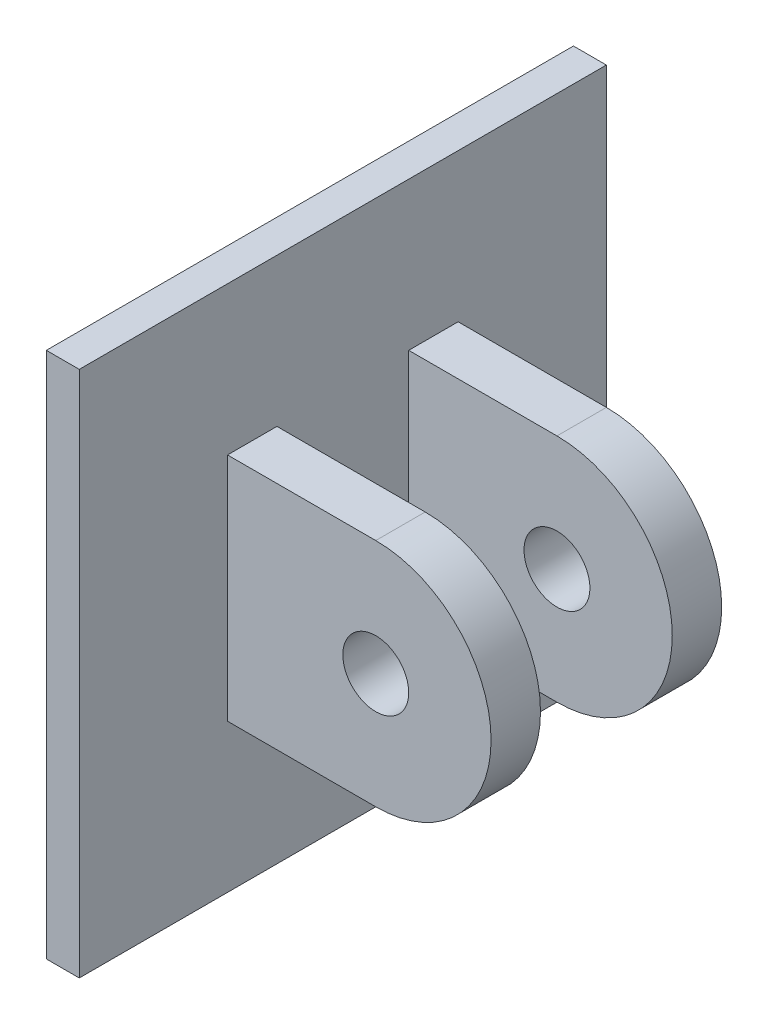
SolidWorks part; units mm, degrees
ref_plane "Front Plane" through (0, 0, 0) normal (0, 0, 1) x (1, 0, 0)
ref_plane "Top Plane" through (0, 0, 0) normal (0, 1, 0) x (1, 0, 0)
ref_plane "Right Plane" through (0, 0, 0) normal (1, 0, 0) x (0, 0, -1)
sketch "Sketch1" plane through (0, 0, 0) normal (1, 0, 0) x (0, -1, 0)
  line L1 (-50.8, -50.8) -> (50.8, -50.8)
  line L2 (-50.8, -50.8) -> (-50.8, 50.8)
  line L3 (-50.8, 50.8) -> (50.8, 50.8)
  line L4 (50.8, -50.8) -> (50.8, 50.8)
  line L5 (-50.8, -50.8) -> (50.8, 50.8) construction
  line L6 (-50.8, 50.8) -> (50.8, -50.8) construction
  dimension "D1" = 101.6
  dimension "D2" = 101.6
extrude "Boss-Extrude1" add sketch "Sketch1" along normal blind 6.35 contours L3 L4 L1 L2
sketch "Sketch2" plane through (6.35, 0, 0) normal (1, 0, 0) x (0, -1, 0)
  line L0 (0, 0) -> (0, 50.8) construction
  line L1 (-50.8, 50.8) -> (50.8, 50.8) construction
  line L2 (0, 0) -> (-50.8, 0) construction
  line L3 (-50.8, -50.8) -> (-50.8, 50.8) construction
  line L4 (-22.225, 12.7) -> (22.225, 22.225) construction
  line L5 (-22.225, 22.225) -> (22.225, 12.7) construction
  line L6 (22.225, 22.225) -> (22.225, 12.7)
  line L7 (-22.225, 12.7) -> (22.225, 12.7)
  line L8 (-22.225, 22.225) -> (-22.225, 12.7)
  line L9 (-22.225, 22.225) -> (22.225, 22.225)
  line L15 (-22.225, -22.225) -> (22.225, -22.225)
  line L16 (-22.225, -22.225) -> (-22.225, -12.7)
  line L17 (-22.225, -12.7) -> (22.225, -12.7)
  line L18 (22.225, -22.225) -> (22.225, -12.7)
  line L19 (-22.225, -22.225) -> (22.225, -12.7) construction
  line L20 (-22.225, -12.7) -> (22.225, -22.225) construction
  point P12 (0, 17.4625)
  point P15 (0, -17.4625)
  dimension "D4" = 44.45
  dimension "D5" = 9.525
  dimension "D6" = 17.4625
extrude "Boss-Extrude2" add sketch "Sketch2" along normal blind 50.8
sketch "Sketch3" plane through (0, 0, -22.225) normal (0, 0, -1) x (0, 1, 0)
  line L6 (-22.225, 6.35) -> (22.225, 6.35)
  line L7 (22.225, 6.35) -> (22.225, 57.15)
  line L8 (22.225, 57.15) -> (-22.225, 57.15)
  line L9 (-22.225, 57.15) -> (-22.225, 6.35)
  line L10 (-22.225, 6.35) -> (22.225, 6.35)
  line L11 (22.225, 6.35) -> (22.225, 57.15)
  line L12 (22.225, 57.15) -> (-22.225, 57.15)
  line L13 (-22.225, 57.15) -> (-22.225, 6.35)
  circle A0 centre (0, 34.925) radius 6.35
  circle A1 centre (0, 34.925) radius 22.225
  line M28 (22.225, 57.15) -> (-22.225, 57.15)
  line M29 (-22.225, 57.15) -> (-22.225, 6.35)
  dimension "D1" = 12.7
  dimension "D2" = 0
extrude "Cut-Extrude1" cut sketch "Sketch3" against normal through all contours M28 | M29 | A0 region at (52.1856, -17.2606, -22.225) region at (52.1856, 17.2606, -22.225) region at (34.925, 0, -22.225)
